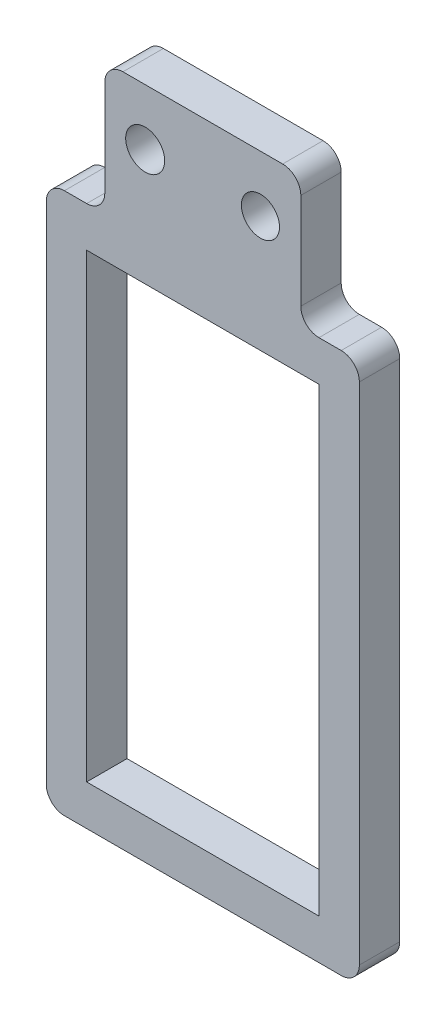
SolidWorks part; units mm, degrees
ref_plane "Front Plane" through (0, 0, 0) normal (0, 0, 1) x (1, 0, 0)
ref_plane "Top Plane" through (0, 0, 0) normal (0, 1, 0) x (1, 0, 0)
ref_plane "Right Plane" through (0, 0, 0) normal (1, 0, 0) x (0, 0, -1)
sketch "Sketch3" plane through (0, 0, 0) normal (0, 0, 1) x (1, 0, 0)
  line L0 (-10.9, -8.375) -> (-10.9, -68.025)
  line L1 (-10.9, -68.025) -> (23.6, -68.025)
  line L2 (23.6, -68.025) -> (23.6, -8.375)
  line L3 (17.15, 6.2) -> (-4.45, 6.2)
  line L4 (12.7, 0) -> (0, 0) construction
  line L5 (-6.45, -63.575) -> (19.15, -63.575)
  line L6 (19.15, -63.575) -> (19.15, -12.825)
  line L7 (19.15, -12.825) -> (-6.45, -12.825)
  line L8 (-6.45, -12.825) -> (-6.45, -63.575)
  line L9 (12.7, -63.175) -> (0, -63.175) construction
  line L10 (12.7, -12.825) -> (0, -12.825) construction
  line L11 (2.9783, 6.2) -> (0, 6.2) construction
  line L12 (6.35, 0) -> (6.35, 6.2) construction
  line L13 (-6.25, -12.825) -> (-6.25, -63.575) construction
  line L14 (18.95, -12.825) -> (18.95, -63.575) construction
  line L15 (-10.9, -8.375) -> (-4.45, -8.375)
  line L16 (-4.45, -8.375) -> (-4.45, 6.2)
  line L17 (17.15, -8.375) -> (17.15, 6.2)
  line L18 (23.6, -8.375) -> (17.15, -8.375)
  circle A0 centre (12.7, 0) radius 2.15
  arc A1 (9.6134, -0.7439) -> (10.1633, 1.9094) centre (12.7, 0) ccw construction
  arc A2 (9.525, 0) -> (15.875, 0) centre (12.7, 0) ccw construction
  arc A3 (15.875, 0) -> (9.525, 0) centre (12.7, 0) ccw construction
  circle A4 centre (0, 0) radius 2.15
  arc M5 (14.8, 0) -> (10.6, 0) centre (12.7, 0) cw
  arc M6 (10.6, 0) -> (14.8, 0) centre (12.7, 0) cw
  dimension "D1" = 4.3
  dimension "D2" = 4.45
  dimension "D3" = 4.45
  dimension "D4" = 4.45
  dimension "D5" = 0.4
  dimension "D6" = 0.2
  dimension "D7" = 0.2
  dimension "D8" = 4.45
  dimension "D9" = 4.45
extrude "Boss-Extrude1" add sketch "Sketch3" along normal blind 4.45 contours A4 | M5 M6 | L7 L8 L5 L6 | L0 L1 L2 L18 L17 L3 L16 L15 region at (6.35, -38.2, 0) region at (0, 0, 0) region at (12.7, 0, 0)
fillet "Fillet1" radius 2 8 edges at (-10.9, -68.025, 2.225) (23.6, -68.025, 2.225) (-10.9, -8.375, 2.225) (23.6, -8.375, 2.225) (17.15, -8.375, 2.225) (17.15, 6.2, 2.225) (-4.45, 6.2, 2.225) (-4.45, -8.375, 2.225)
